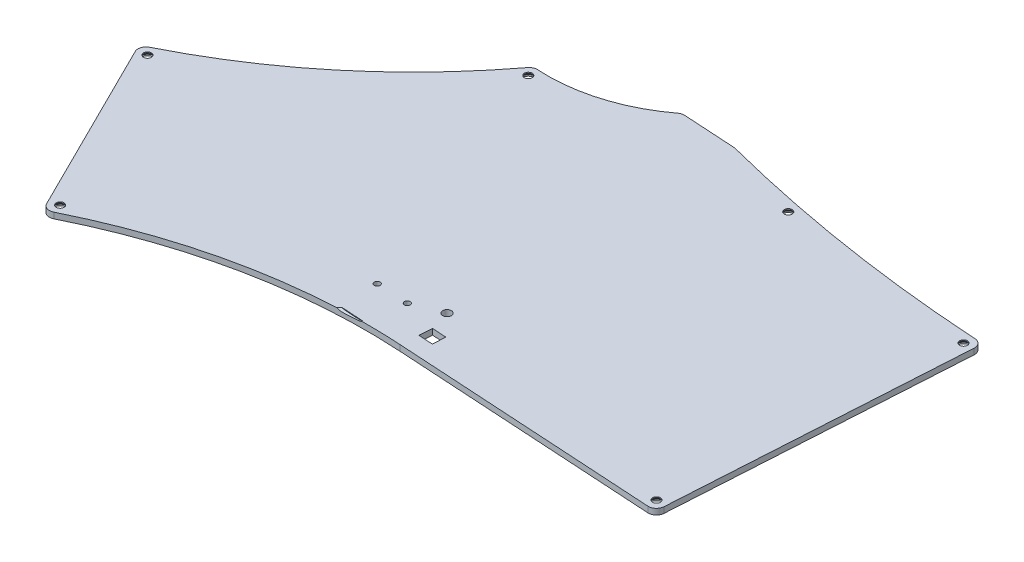
SolidWorks part; units mm, degrees
ref_plane "Front Plane" through (0, 0, 0) normal (0, 0, 1) x (1, 0, 0)
ref_plane "Top Plane" through (0, 0, 0) normal (0, 1, 0) x (1, 0, 0)
ref_plane "Right Plane" through (0, 0, 0) normal (1, 0, 0) x (0, 0, -1)
sketch "Main_line" plane through (0, 0, 0) normal (0, 1, 0) x (1, 0, 0)
  line L0 (47.5657, -117.8094) -> (51.8578, -118.0699) construction
  line L9 (47.2541, -117.9909) -> (52.1451, -118.2877) construction
  line L10 (47.2541, -117.9909) -> (47.5207, -113.5989) construction
  line L11 (47.5207, -113.5989) -> (52.4117, -113.8958) construction
  line L12 (52.1451, -118.2877) -> (52.4117, -113.8958) construction
  line L13 (47.2541, -117.9909) -> (52.4117, -113.8958) construction
  line L14 (47.5207, -113.5989) -> (52.1451, -118.2877) construction
  line L15 (51.9637, -117.9762) -> (52.1939, -114.1831) construction
  line L16 (52.1001, -114.0773) -> (47.808, -113.8168) construction
  line L17 (47.7022, -113.9105) -> (47.472, -117.7035) construction
  line L57 (46.7162, -124.1696) -> (137.2622, -129.6653)
  line L58 (-85.9719, -82.3907) -> (-55.9349, -142.8392)
  line L59 (45.4717, -7.8806) -> (27.5047, -6.7901)
  line L60 (140.4384, -126.8525) -> (146.527, -26.5371)
  line L61 (46.7162, -124.1696) -> (137.2622, -129.6653) construction
  line L62 (-85.9719, -82.3907) -> (-55.9349, -142.8392) construction
  line L63 (45.4717, -7.8806) -> (27.5047, -6.7901) construction
  line L64 (140.4384, -126.8525) -> (146.527, -26.5371) construction
  circle A0 centre (45.4932, -106.5632) radius 1.5 construction
  circle A1 centre (35.7393, -110.4594) radius 1 construction
  circle A2 centre (24.7595, -109.793) radius 1 construction
  circle A3 centre (-11.2177, -21.9715) radius 1.35 construction
  circle A5 centre (45.4932, -106.5632) radius 1.5 construction
  circle A18 centre (-82.6154, -81.2804) radius 1.35 construction
  arc A121 (137.2622, -129.6653) -> (140.4384, -126.8525) centre (137.444, -126.6708) ccw
  arc A122 (46.7162, -124.1696) -> (-51.9133, -144.1909) centre (34.8975, -318.8948) ccw
  arc A123 (-55.9349, -142.8392) -> (-51.9133, -144.1909) centre (-53.2483, -141.5043) ccw
  arc A124 (-84.6203, -78.3691) -> (-85.9719, -82.3907) centre (-83.2853, -81.0557) ccw
  arc A125 (-84.6203, -78.3691) -> (-13.8495, -19.649) centre (-173.8216, 101.1455) ccw
  arc A126 (-11.2736, -18.4623) -> (-13.8495, -19.649) centre (-11.4554, -21.4568) ccw
  arc A127 (-11.2736, -18.4623) -> (25.5185, -7.388) centre (-7.907, 37.0071) ccw
  arc A128 (27.5047, -6.7901) -> (25.5185, -7.388) centre (27.323, -9.7846) ccw
  arc A129 (46.0378, -7.9698) -> (45.4717, -7.8806) centre (45.2899, -10.8751) ccw
  arc A130 (46.0378, -7.9698) -> (143.7143, -23.3609) centre (175.0715, 493.2805) ccw
  arc A131 (146.527, -26.5371) -> (143.7143, -23.3609) centre (143.5325, -26.3554) ccw
  arc A132 (137.2622, -129.6653) -> (140.4384, -126.8525) centre (137.444, -126.6708) ccw construction
  arc A133 (46.7162, -124.1696) -> (-51.9133, -144.1909) centre (34.8975, -318.8948) ccw construction
  arc A134 (-55.9349, -142.8392) -> (-51.9133, -144.1909) centre (-53.2483, -141.5043) ccw construction
  circle A146 centre (136.9752, -126.1414) radius 1.35 construction
  circle A149 centre (-53.0228, -140.8346) radius 1.35 construction
  circle A150 centre (-82.6154, -81.2804) radius 1.35 construction
  circle A151 centre (-11.2177, -21.9715) radius 1.35 construction
  circle A152 centre (73.917, -17.8993) radius 1.35 construction
  circle A153 centre (143.0032, -26.8239) radius 1.35 construction
  arc A154 (-84.6203, -78.3691) -> (-85.9719, -82.3907) centre (-83.2853, -81.0557) ccw construction
  arc A155 (-84.6203, -78.3691) -> (-13.8495, -19.649) centre (-173.8216, 101.1455) ccw construction
  arc A156 (-11.2736, -18.4623) -> (-13.8495, -19.649) centre (-11.4554, -21.4568) ccw construction
  arc A157 (-11.2736, -18.4623) -> (25.5185, -7.388) centre (-7.907, 37.0071) ccw construction
  arc A158 (27.5047, -6.7901) -> (25.5185, -7.388) centre (27.323, -9.7846) ccw construction
  arc A159 (46.0378, -7.9698) -> (45.4717, -7.8806) centre (45.2899, -10.8751) ccw construction
  arc A160 (46.0378, -7.9698) -> (143.7143, -23.3609) centre (175.0715, 493.2805) ccw construction
  arc A161 (146.527, -26.5371) -> (143.7143, -23.3609) centre (143.5325, -26.3554) ccw construction
  point P23 (49.8329, -115.9433)
  dimension "D2" = 2
  dimension "D3" = 0.2
  dimension "D4" = 3
  dimension "D5" = 0.2
  dimension "D6" = 0.2
  dimension "D7" = 0.2
  dimension "D1" = 0
sketch "Sketch1" plane through (0, 0, 0) normal (0, 1, 0) x (1, 0, 0)
  line L0 (47.5207, -113.5989) -> (52.4117, -113.8958)
  line L1 (47.5207, -113.5989) -> (47.2541, -117.9909)
  line L2 (52.4117, -113.8958) -> (52.1451, -118.2877)
  line L3 (47.2541, -117.9909) -> (52.1451, -118.2877)
  line L33 (-85.7928, -82.3017) -> (-55.7558, -142.7502)
  line L34 (46.7283, -123.97) -> (137.2743, -129.4656)
  line L35 (140.2388, -126.8404) -> (146.3274, -26.525)
  line L36 (45.4595, -8.0803) -> (27.4926, -6.9898)
  line L37 (-85.7928, -82.3017) -> (-55.7558, -142.7502)
  line L38 (46.7283, -123.97) -> (137.2743, -129.4656)
  line L39 (140.2388, -126.8404) -> (146.3274, -26.525)
  line L40 (45.4595, -8.0803) -> (27.4926, -6.9898)
  circle A2 centre (-53.0228, -140.8346) radius 1.35 construction
  circle A3 centre (24.7595, -109.793) radius 1
  circle A4 centre (35.7393, -110.4594) radius 1
  circle A5 centre (45.4932, -106.5632) radius 1.5
  circle A6 centre (45.4932, -106.5632) radius 1.5 construction
  circle A7 centre (35.7393, -110.4594) radius 1 construction
  circle A8 centre (24.7595, -109.793) radius 1 construction
  circle A93 centre (143.0032, -26.8239) radius 1.35
  circle A94 centre (143.0032, -26.8239) radius 1.35 construction
  circle A95 centre (73.917, -17.8993) radius 1.35
  circle A96 centre (-11.2177, -21.9715) radius 1.35
  circle A97 centre (-82.6154, -81.2804) radius 1.35
  circle A98 centre (-53.0228, -140.8346) radius 1.35
  circle A100 centre (136.9752, -126.1414) radius 1.35
  arc A139 (-84.5313, -78.5482) -> (-85.7928, -82.3017) centre (-83.2853, -81.0557) ccw
  arc A140 (-55.7558, -142.7502) -> (-52.0023, -144.0118) centre (-53.2483, -141.5043) ccw
  arc A141 (46.7283, -123.97) -> (-52.0023, -144.0118) centre (34.8975, -318.8948) ccw
  arc A142 (137.2743, -129.4656) -> (140.2388, -126.8404) centre (137.444, -126.6708) ccw
  arc A143 (146.3274, -26.525) -> (143.7022, -23.5605) centre (143.5325, -26.3554) ccw
  arc A144 (45.9879, -8.1635) -> (143.7022, -23.5605) centre (175.0715, 493.2805) ccw
  arc A145 (45.9879, -8.1635) -> (45.4595, -8.0803) centre (45.2899, -10.8751) ccw
  arc A146 (27.4926, -6.9898) -> (25.6388, -7.5477) centre (27.323, -9.7846) ccw
  arc A147 (-11.2858, -18.6619) -> (25.6388, -7.5477) centre (-7.907, 37.0071) ccw
  arc A148 (-11.2858, -18.6619) -> (-13.6899, -19.7695) centre (-11.4554, -21.4568) ccw
  arc A149 (-84.5313, -78.5482) -> (-13.6899, -19.7695) centre (-173.8216, 101.1455) ccw
  arc A150 (-84.5313, -78.5482) -> (-85.7928, -82.3017) centre (-83.2853, -81.0557) ccw
  arc A151 (-55.7558, -142.7502) -> (-52.0023, -144.0118) centre (-53.2483, -141.5043) ccw
  arc A152 (46.7283, -123.97) -> (-52.0023, -144.0118) centre (34.8975, -318.8948) ccw
  arc A153 (137.2743, -129.4656) -> (140.2388, -126.8404) centre (137.444, -126.6708) ccw
  arc A154 (146.3274, -26.525) -> (143.7022, -23.5605) centre (143.5325, -26.3554) ccw
  arc A155 (45.9879, -8.1635) -> (143.7022, -23.5605) centre (175.0715, 493.2805) ccw
  arc A156 (45.9879, -8.1635) -> (45.4595, -8.0803) centre (45.2899, -10.8751) ccw
  arc A157 (27.4926, -6.9898) -> (25.6388, -7.5477) centre (27.323, -9.7846) ccw
  arc A158 (-11.2858, -18.6619) -> (25.6388, -7.5477) centre (-7.907, 37.0071) ccw
  arc A159 (-11.2858, -18.6619) -> (-13.6899, -19.7695) centre (-11.4554, -21.4568) ccw
  arc A160 (-84.5313, -78.5482) -> (-13.6899, -19.7695) centre (-173.8216, 101.1455) ccw
  dimension "D1" = 0.2
extrude "Main_plate" add sketch "Sketch1" along normal blind 2
sketch "Sketch2" plane through (0, 0, 0) normal (0, -1, 0) x (1, 0, 0)
  circle A0 centre (136.9752, 126.1414) radius 2.5
  circle A2 centre (-53.0228, 140.8346) radius 2.5
  circle A3 centre (-82.6154, 81.2804) radius 2.5
  circle A4 centre (-11.2177, 21.9715) radius 2.5
  circle A5 centre (73.917, 17.8993) radius 2.5
  circle A6 centre (143.0032, 26.8239) radius 2.5
  dimension "D1" = 5
extrude "Screw_holes" cut sketch "Sketch2" against normal blind 1.7
chamfer "Screw_holes_chamfer" distance 1.2 angle 45 6 edges at (143.0032, 1.7, 24.3239) (73.917, 1.7, 15.3993) (-11.2177, 1.7, 19.4715) (-82.6154, 1.7, 78.7804) (-53.0228, 1.7, 138.3346) (136.9752, 1.7, 123.6414)
ref_plane "Charge_port_plane1" through (-7.3373, 0, 120.8889) normal (-0.0606, 0, 0.9982) x (0.9982, 0, 0.0606)
ref_plane "Charge_port_plane2" through (-7.6402, 0, 125.8797) normal (-0.0606, 0, 0.9982) x (0.9982, 0, 0.0606)
sketch "Sketch3" plane through (-7.3373, 0, 120.8889) normal (-0.0606, 0, 0.9982) x (0.9982, 0, 0.0606)
  line L0 (34.4656, 5.5) -> (39.2656, 5.5) construction
  line L1 (34.4656, 9.25) -> (39.2656, 9.25)
  line L2 (34.4656, 1.75) -> (39.2656, 1.75)
  line L3 (-43.1822, 0) -> (54.1529, 0) construction
  line L4 (147.6656, 2) -> (147.6656, 0) construction
  arc A0 (34.4656, 9.25) -> (34.4656, 1.75) centre (34.4656, 5.5) ccw
  arc A1 (39.2656, 1.75) -> (39.2656, 9.25) centre (39.2656, 5.5) ccw
  point P2 (36.8656, 5.5)
  point P7 (37.3908, -2.888)
  point P8 (32.9069, -2.7334)
  point P9 (40.4832, -2.5788)
  point P10 (39.2656, 5.5)
  point P11 (34.4656, 5.5)
  point P12 (0, 0)
  point P17 (39.2656, 10.75)
  point P18 (39.2656, 9.25)
  dimension "D1" = 4.8
  dimension "D2" = 5.5
  dimension "D3" = 110.8
  dimension "D4" = 7.5
sketch "Sketch4" plane through (-7.6402, 0, 125.8797) normal (-0.0606, 0, 0.9982) x (0.9982, 0, 0.0606)
  line L0 (34.4656, 5.5) -> (39.2656, 5.5) construction
  line L1 (34.4656, 10.75) -> (39.2656, 10.75)
  line L2 (34.4656, 0.25) -> (39.2656, 0.25)
  arc A0 (34.4656, 10.75) -> (34.4656, 0.25) centre (34.4656, 5.5) ccw
  arc A1 (39.2656, 0.25) -> (39.2656, 10.75) centre (39.2656, 5.5) ccw
  point P4 (36.8656, 5.5)
  point P9 (39.2656, 5.5)
  dimension "D1" = 10.5
loft "Cut-Loft1" cut profiles "Sketch4", "Sketch3" connector at (26.7621, 10.75, 127.9677) connector at (27.065, 9.25, 122.9769)
